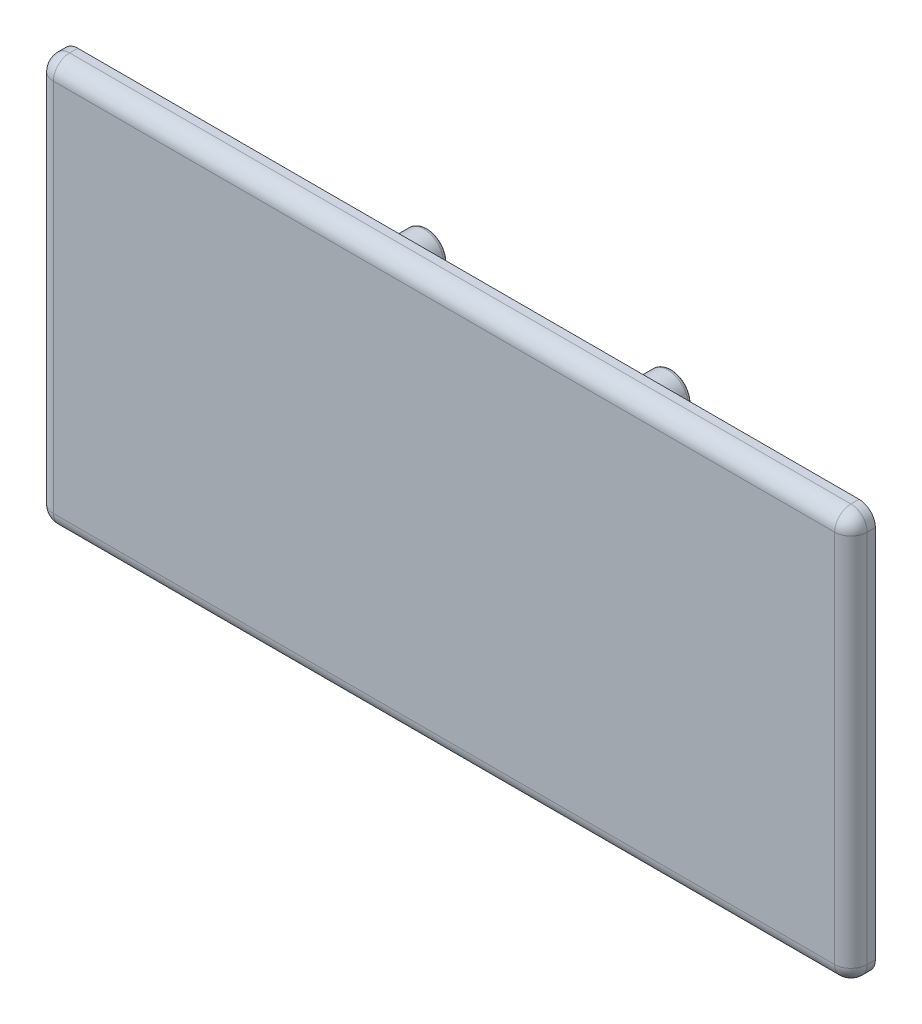
SolidWorks part; units mm, degrees
ref_plane "Front Plane" through (0, 0, 0) normal (0, 0, 1) x (1, 0, 0)
ref_plane "Top Plane" through (0, 0, 0) normal (0, 1, 0) x (1, 0, 0)
ref_plane "Right Plane" through (0, 0, 0) normal (1, 0, 0) x (0, 0, -1)
sketch "Sketch1" plane through (0, 0, 0) normal (0, 0, 1) x (1, 0, 0)
  line L4 (-48, -25) -> (48, -25)
  line L5 (50, -23) -> (50, 23)
  line L6 (48, 25) -> (-48, 25)
  line L7 (-50, 23) -> (-50, -23)
  line L8 (-48, -25) -> (48, -25)
  line L9 (50, -23) -> (50, 23)
  line L10 (48, 25) -> (-48, 25)
  line L11 (-50, 23) -> (-50, -23)
  arc A4 (48, -25) -> (50, -23) centre (48, -23) ccw
  arc A5 (50, 23) -> (48, 25) centre (48, 23) ccw
  arc A6 (-48, 25) -> (-50, 23) centre (-48, 23) ccw
  arc A7 (-50, -23) -> (-48, -25) centre (-48, -23) ccw
  arc A8 (48, -25) -> (50, -23) centre (48, -23) ccw
  arc A9 (50, 23) -> (48, 25) centre (48, 23) ccw
  arc A10 (-48, 25) -> (-50, 23) centre (-48, 23) ccw
  arc A11 (-50, -23) -> (-48, -25) centre (-48, -23) ccw
  dimension "D1" = 0
extrude "Boss-Extrude1" add sketch "Sketch1" along normal blind 3
fillet "Fillet1" radius 2 8 edges at (-50, 0, 3) (-49.4142, 24.4142, 3) (0, 25, 3) (49.4142, 24.4142, 3) (50, 0, 3) (49.4142, -24.4142, 3) (0, -25, 3) (-49.4142, -24.4142, 3)
sketch "Sketch2" plane through (0, 0, 0) normal (0, 0, -1) x (-1, 0, 0)
  line L0 (-25, -18.5) -> (-25, -21.5)
  line L1 (-35, -18.5) -> (-35, -21.5)
  line L2 (25, -18.5) -> (25, -21.5)
  line L3 (35, -18.5) -> (35, -21.5)
  line L4 (50, -23) -> (50, 23)
  line L5 (48, 25) -> (-48, 25)
  line L6 (-50, 23) -> (-50, -23)
  line L7 (-48, -25) -> (48, -25)
  line L8 (50, -23) -> (50, 23)
  line L9 (48, 25) -> (-48, 25)
  line L10 (-50, 23) -> (-50, -23)
  line L11 (-48, -25) -> (48, -25)
  line L12 (50, -23) -> (50, 23)
  line L13 (48, 25) -> (-48, 25)
  line L14 (-50, 23) -> (-50, -23)
  line L15 (-48, -25) -> (48, -25)
  line L16 (50, -23) -> (50, 23)
  line L17 (48, 25) -> (-48, 25)
  line L18 (-50, 23) -> (-50, -23)
  line L19 (-48, -25) -> (48, -25)
  line L20 (25, 18.5) -> (25, 21.5)
  line L21 (35, 18.5) -> (35, 21.5)
  line L22 (43.5, -10) -> (46.5, -10)
  line L23 (43.5, 10) -> (46.5, 10)
  line L24 (-46.5, -21.5) -> (46.5, -21.5)
  line L25 (-46.5, 21.5) -> (-46.5, -21.5)
  line L26 (46.5, 21.5) -> (-46.5, 21.5)
  line L27 (46.5, -21.5) -> (46.5, 21.5)
  line L28 (-46.5, -21.5) -> (46.5, -21.5)
  line L29 (-46.5, 21.5) -> (-46.5, -21.5)
  line L30 (46.5, 21.5) -> (-46.5, 21.5)
  line L31 (46.5, -21.5) -> (46.5, 21.5)
  line L32 (43.5, -18.5) -> (43.5, 18.5)
  line L33 (43.5, 18.5) -> (-43.5, 18.5)
  line L34 (-43.5, 18.5) -> (-43.5, -18.5)
  line L35 (-43.5, -18.5) -> (43.5, -18.5)
  line L36 (-43.5, -10) -> (-43.5, 10)
  line L37 (-25, 18.5) -> (-35, 18.5)
  line L38 (-43.5, 10) -> (-46.5, 10)
  line L39 (-43.5, 10) -> (-43.5, -10)
  line L40 (-43.5, -10) -> (-46.5, -10)
  line L41 (-46.5, 10) -> (-46.5, -10)
  line L42 (43.5, 0) -> (-46.5, 0) construction
  line L43 (-25, 18.5) -> (-35, 18.5)
  line L44 (-25, 18.5) -> (-25, 21.5)
  line L45 (-25, 21.5) -> (-35, 21.5)
  line L46 (-35, 18.5) -> (-35, 21.5)
  line L47 (0, 18.5) -> (0, -18.5) construction
  arc A4 (48, -25) -> (50, -23) centre (48, -23) ccw
  arc A5 (50, 23) -> (48, 25) centre (48, 23) ccw
  arc A6 (-48, 25) -> (-50, 23) centre (-48, 23) ccw
  arc A7 (-50, -23) -> (-48, -25) centre (-48, -23) ccw
  arc A8 (48, -25) -> (50, -23) centre (48, -23) ccw
  arc A9 (50, 23) -> (48, 25) centre (48, 23) ccw
  arc A10 (-48, 25) -> (-50, 23) centre (-48, 23) ccw
  arc A11 (-50, -23) -> (-48, -25) centre (-48, -23) ccw
  arc A12 (50, 23) -> (48, 25) centre (48, 23) ccw
  arc A13 (-48, 25) -> (-50, 23) centre (-48, 23) ccw
  arc A14 (-50, -23) -> (-48, -25) centre (-48, -23) ccw
  arc A15 (48, -25) -> (50, -23) centre (48, -23) ccw
  arc A16 (50, 23) -> (48, 25) centre (48, 23) ccw
  arc A17 (-48, 25) -> (-50, 23) centre (-48, 23) ccw
  arc A18 (-50, -23) -> (-48, -25) centre (-48, -23) ccw
  arc A19 (48, -25) -> (50, -23) centre (48, -23) ccw
  point P24 (-43.5, 0)
  point P29 (-30, 18.5)
  point P35 (0, 0)
  dimension "D5" = 20
  dimension "D6" = 10
  dimension "D7" = 11.5
  dimension "D1" = 0
  dimension "D2" = 0
  dimension "D3" = 3.5
  dimension "D4" = 3
extrude "Boss-Extrude2" add sketch "Sketch2" along normal blind 1.5 contours L46 L33 L44 L30 | L40 L34 L38 L29 | L35 L1 L28 L0 | L35 L2 L28 L3 | L32 L22 L31 L23 | L33 L21 L30 L20 region at (30, -20, 0) region at (-30, -20, 0) region at (45, 0, 0) region at (-45, 0, 0) region at (30, 20, 0) region at (-30, 20, 0)
fillet "Fillet2" radius 1 48 edges at (-25, 20, -1.5) (-30, 21.5, -1.5) (-35, 20, -1.5) (-30, 18.5, -1.5) (-35, -20, -1.5) (-30, -21.5, -1.5) (-25, -20, -1.5) (-30, -18.5, -1.5) (-45, 10, -1.5) (-46.5, 0, -1.5) (-45, -10, -1.5) (-43.5, 0, -1.5) (25, -20, -1.5) (30, -21.5, -1.5) (35, -20, -1.5) (30, -18.5, -1.5) (46.5, 0, -1.5) (45, 10, -1.5) (43.5, 0, -1.5) (45, -10, -1.5) (30, 21.5, -1.5) (25, 20, -1.5) (30, 18.5, -1.5) (35, 20, -1.5) (-25, 21.5, -0.75) (-35, 21.5, -0.75) (-35, 18.5, -0.75) (-25, 18.5, -0.75) (-25, -18.5, -0.75) (-25, -21.5, -0.75) (-35, -21.5, -0.75) (-35, -18.5, -0.75) (-46.5, -10, -0.75) (-43.5, -10, -0.75) (-46.5, 10, -0.75) (-43.5, 10, -0.75) (25, -18.5, -0.75) (25, -21.5, -0.75) (35, -18.5, -0.75) (35, -21.5, -0.75) (25, 21.5, -0.75) (25, 18.5, -0.75) (35, 21.5, -0.75) (35, 18.5, -0.75) (43.5, 10, -0.75) (46.5, 10, -0.75) (46.5, -10, -0.75) (43.5, -10, -0.75)
sketch "Sketch3" plane through (0, 0, 0) normal (0, 0, -1) x (-1, 0, 0)
  line L4 (50, -23) -> (50, 23)
  line L5 (48, 25) -> (-48, 25)
  line L6 (-50, 23) -> (-50, -23)
  line L7 (-48, -25) -> (48, -25)
  line L8 (50, -23) -> (50, 23)
  line L9 (48, 25) -> (-48, 25)
  line L10 (-50, 23) -> (-50, -23)
  line L11 (-48, -25) -> (48, -25)
  circle A0 centre (-15, -15) radius 3.0099 construction
  circle A1 centre (-15, 15) radius 3.0099 construction
  circle A2 centre (15, -15) radius 3.0099 construction
  circle A3 centre (15, 15) radius 3.0099 construction
  arc A4 (48, -25) -> (50, -23) centre (48, -23) ccw
  arc A5 (50, 23) -> (48, 25) centre (48, 23) ccw
  arc A6 (-48, 25) -> (-50, 23) centre (-48, 23) ccw
  arc A7 (-50, -23) -> (-48, -25) centre (-48, -23) ccw
  arc A8 (48, -25) -> (50, -23) centre (48, -23) ccw
  arc A9 (50, 23) -> (48, 25) centre (48, 23) ccw
  arc A10 (-48, 25) -> (-50, 23) centre (-48, 23) ccw
  arc A11 (-50, -23) -> (-48, -25) centre (-48, -23) ccw
  circle A12 centre (-15, -15) radius 3.0099 construction
  circle A13 centre (-15, 15) radius 3.0099 construction
  circle A14 centre (15, -15) radius 3.0099 construction
  circle A15 centre (15, 15) radius 3.0099 construction
  circle A16 centre (-15, 15) radius 2.5099
  circle A17 centre (-15, -15) radius 2.5099
  circle A18 centre (15, -15) radius 2.5099
  circle A19 centre (15, 15) radius 2.5099
  point P32 (0, 0)
  dimension "D1" = 0
  dimension "D2" = 0.5
extrude "Boss-Extrude3" add sketch "Sketch3" along normal blind 10 contours A17 | A16 | A18 | A19 region at (15, 15, 0) region at (15, -15, 0) region at (-15, -15, 0) region at (-15, 15, 0)
fillet "Fillet3" radius 0.5 4 edges at (12.4901, 15, -10) (-17.5099, -15, -10) (-17.5099, 15, -10) (12.4901, -15, -10)
